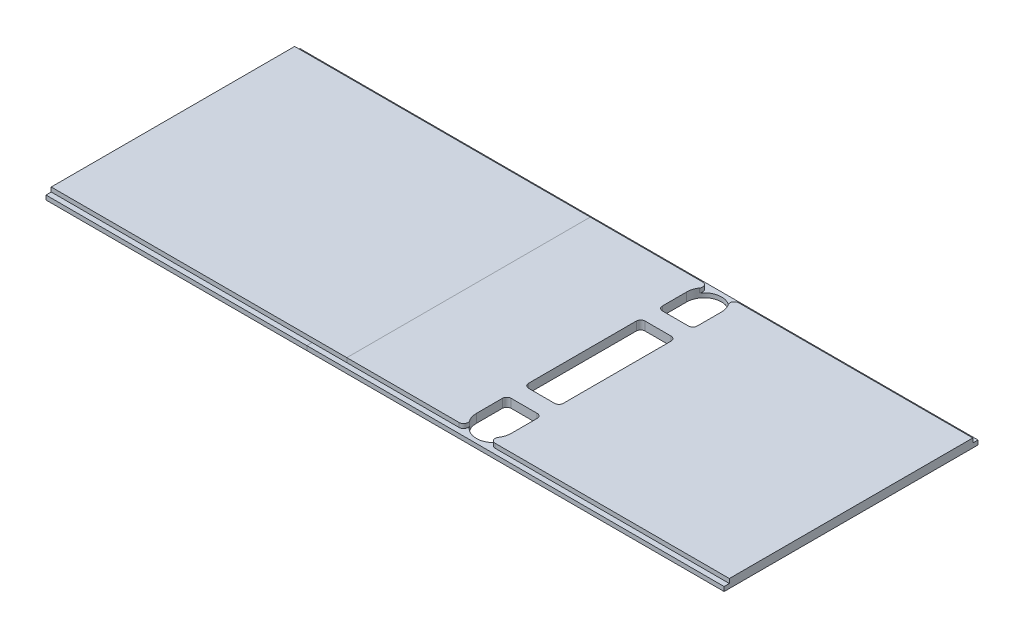
SolidWorks part; units mm, degrees
ref_plane "Front Plane" through (0, 0, 0) normal (0, 0, 1) x (1, 0, 0)
ref_plane "Top Plane" through (0, 0, 0) normal (0, 1, 0) x (1, 0, 0)
ref_plane "Right Plane" through (0, 0, 0) normal (1, 0, 0) x (0, 0, -1)
sketch "Sketch16" plane through (0, 0, 0) normal (0, 1, 0) x (1, 0, 0)
  line L0 (74.8974, -12.5) -> (55.1026, -12.5)
  line L1 (-180, 0) -> (210, 0)
  line L2 (-180, 0) -> (-180, -146)
  line L3 (-180, -146) -> (210, -146)
  line L4 (210, 0) -> (210, -146)
  line L5 (75, -133.5) -> (55, -133.5)
  line L6 (65, -133.5) -> (65, -12.5) construction
  line L7 (55, -133.5) -> (55, -12.5)
  line L8 (75, -133.5) -> (75, -12.5)
  line L9 (-30, -146) -> (-30, 0)
  line L10 (-180, -143) -> (210, -143)
  line L11 (-180, -143) -> (-180, -3)
  line L12 (-180, -3) -> (210, -3)
  line L13 (210, -143) -> (210, -3)
  line L14 (-10, -146) -> (-10, 0)
  arc A0 (55, -133.5) -> (75, -133.5) centre (65, -133.5) ccw
  arc A1 (75, -12.5) -> (55, -12.5) centre (65, -12.5) ccw
  point P16 (65, -73)
  dimension "D1" = 10
  dimension "D2" = 12.5
  dimension "D3" = 12.5
  dimension "D4" = 65
  dimension "D5" = 390
  dimension "D6" = 146
  dimension "D7" = 140
  dimension "D8" = 3
  dimension "D9" = 180
  dimension "D10" = 150
  dimension "D11" = 20
extrude "Boss-Extrude4" add sketch "Sketch16" along normal blind 5 separate body contours A1 L12 L2 L10 A0 L7 | A1 L8 A0 L10 L4 L12 region at (22.6316, 0, 73) region at (142.3718, 0, 73)
extrude "Boss-Extrude5" add sketch "Sketch16<5>" along normal blind 2.5 contours A0 L10 L2 L3 L4 | A1 L12 L4 L1 L2 | L3 L14 L10 L9 | L12 L14 L1 L9 | L10 L14 L12 L9 region at (-20, 0, 1.5) region at (100.1113, 0, 1.4959) region at (-20, 0, 73) region at (-20, 0, 144.5) region at (100.1113, 0, 144.5041)
sketch "Sketch16<5>" plane through (0, 0, 0) normal (0, 1, 0) x (1, 0, 0) same geometry as "Sketch16"
sketch "Sketch18" plane through (0, 0, 0) normal (0, -1, 0) x (1, 0, 0)
  line L0 (55, 133.5) -> (55, 12.5) construction
  line L3 (55, 106) -> (75, 106)
  line L11 (55, 106) -> (55, 116)
  line L12 (55, 116) -> (75, 116)
  line L13 (75, 106) -> (75, 116)
  line L14 (75, 133.5) -> (75, 12.5) construction
  line L16 (75, 39) -> (55, 39)
  line L17 (75, 39) -> (75, 29)
  line L18 (75, 29) -> (55, 29)
  line L19 (55, 39) -> (55, 29)
  line L21 (-30, 146) -> (210, 146) construction
  point P14 (0, 0)
  line M8 (55, 12.5) -> (55, 133.5)
  line M10 (75, 133.5) -> (75, 12.5)
  dimension "D1" = 10
  dimension "D2" = 10
  dimension "D3" = 67
  dimension "D4" = 30
extrude "Boss-Extrude6" add sketch "Sketch18" against normal blind 5 contours L18 L16 M10 M8 | L12 L3 M8 M10 region at (65, 0, 111) region at (65, 0, 34)
fillet "Fillet4" radius 2.5 8 edges at (75, 2.5, 116) (55, 2.5, 116) (75, 2.5, 39) (55, 2.5, 39) (55, 2.5, 106) (75, 2.5, 106) (75, 2.5, 29) (55, 2.5, 29)
fillet "Fillet5" radius 2.5 4 edges at (68.1225, 3.75, 3) (61.8775, 3.75, 3) (68.1225, 3.75, 143) (61.8775, 3.75, 143)
extrude "Boss-Extrude7" add sketch "Sketch16<6>" along normal blind 5 separate body contours L12 L2 L10 L9 | L10 L14 L12 L9 region at (-105, 0, 73) region at (-20, 0, 73)
sketch "Sketch16<6>" plane through (0, 0, 0) normal (0, 1, 0) x (1, 0, 0) same geometry as "Sketch16"
sketch "Sketch19" plane through (0, 0, 143) normal (0, 0, 1) x (1, 0, 0)
  line L0 (-180, 0) -> (210, 0) construction
  line L1 (-10, 2.5) -> (-30, 2.5)
  line L2 (-10, 2.5) -> (-10, 0)
  line L3 (-10, 0) -> (-30, 0)
  line L4 (-30, 2.5) -> (-30, 0)
  dimension "D1" = 20
extrude "Cut-Extrude1" cut sketch "Sketch19" against normal blind 140
extrude "Boss-Extrude8" add sketch "Sketch16<7>" along normal blind 2.5 contours L10 L2 L3 L9 | L2 L12 L9 L1 region at (-105, 0, 1.5) region at (-105, 0, 144.5)
sketch "Sketch16<7>" plane through (0, 0, 0) normal (0, 1, 0) x (1, 0, 0) same geometry as "Sketch16"
